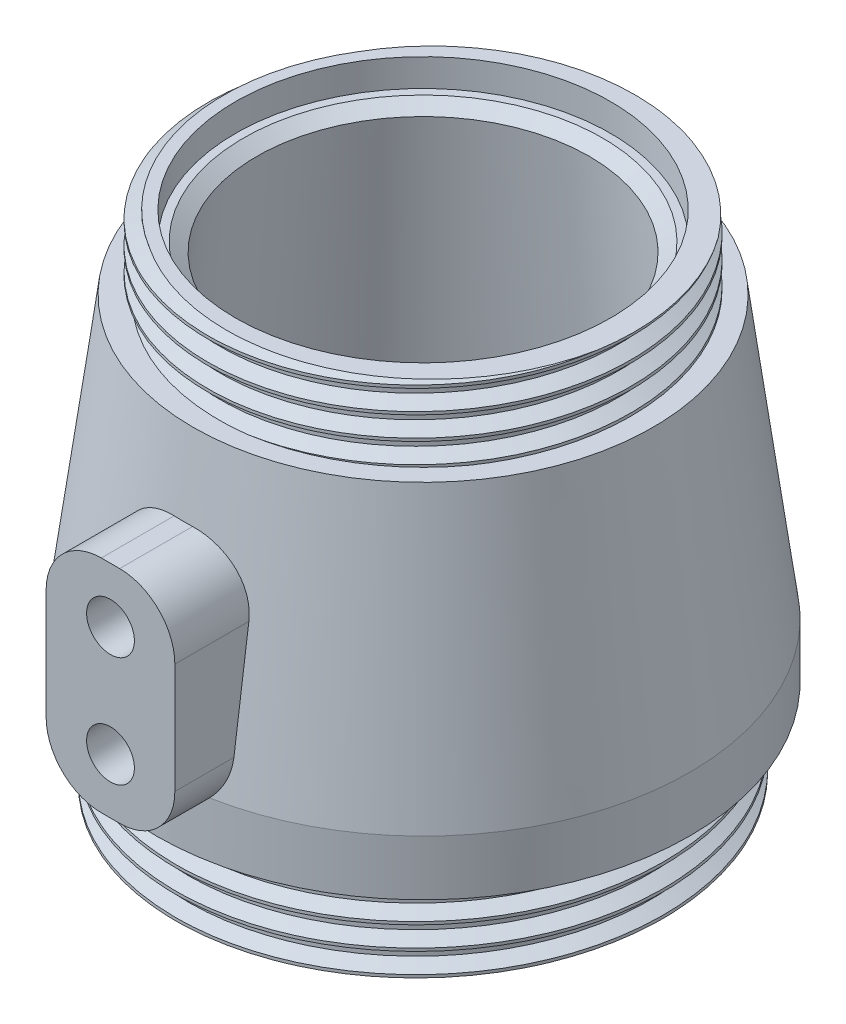
SolidWorks part; units mm, degrees
ref_plane "前视基准面" through (0, 0, 0) normal (0, 0, 1) x (1, 0, 0)
ref_plane "上视基准面" through (0, 0, 0) normal (0, 1, 0) x (1, 0, 0)
ref_plane "右视基准面" through (0, 0, 0) normal (1, 0, 0) x (0, 0, -1)
other "Configuration Table"
sketch "草图1" plane through (0, 0, 0) normal (0, 1, 0) x (1, 0, 0)
  circle A0 centre (0, 0) radius 13.25
  circle A1 centre (0, 0) radius 11
  dimension "D1" = 26.5
  dimension "D2" = 22
extrude "凸台-拉伸1" add sketch "草图1" along normal blind 25.75
sketch "草图2" plane through (0, 25.75, 0) normal (0, 1, 0) x (1, 0, 0)
  circle A0 centre (0, 0) radius 14.5
  circle A1 centre (0, 0) radius 13.25 construction
  circle A2 centre (0, 0) radius 13.25
  dimension "D1" = 29
extrude "凸台-拉伸2" add sketch "草图2" against normal offset from surface (20.75 mm away) 5 up to face at (0, 0, 13.25)
thread "螺纹线1" pitch 1.25 method cut trim with start face yes trim with end face yes profile "螺纹线轮廓1" start angle 0, offset 3, length 0, pitch 1.25, diameter 26.5
ref_plane "基准面1" through (13.25, -3, 0) normal (0, 0, 1) x (1, 0, 0)
sketch "螺纹线轮廓1" plane through (13.25, -3, 0) normal (0, 0, 1) x (1, 0, 0)
  line L0 (0, 0) -> (0, 1.25) construction
  line L11 (0, 0) -> (0, 1.0937)
  line L12 (0, 1.0937) -> (-0.6766, 0.7031)
  line L13 (-0.6766, 0.7031) -> (-0.6766, 0.3906)
  line L15 (-0.6766, 0.3906) -> (0, 0)
  line L17 (-0.6766, 0.5469) -> (0, 0.5469) construction
  point P2 (0, 0)
  dimension "Pitch" = 1.25
  dimension "Profile_Angle" = 60
  dimension "Profile_Land" = 0.3125
  dimension "Profile_Height" = 0.6766
sketch "草图5" plane through (0, 0, 0) normal (1, 0, 0) x (0, 0, -1)
  line L0 (9, 25.75) -> (11, 0)
  line L2 (11, 25.75) -> (-11, 25.75) construction
  line L3 (11, 0) -> (11, 25.75)
  line L4 (11, 25.75) -> (9, 25.75)
  line L6 (0, 0) -> (0, 25.75) construction
  dimension "D1" = 9
revolve "旋转1" add sketch "草图5" angle 360 about L6
chamfer "倒角1" distance 0.5 angle 60 1 edges at (0, 25.75, -9) first distance on face at (0, 0, -11)
sketch "草图6" plane through (0, 25.75, 0) normal (0, 1, 0) x (1, 0, 0)
  circle A0 centre (0, 0) radius 10.2
  circle A1 centre (0, 0) radius 11.5
  dimension "D1" = 20.4
  dimension "D2" = 23
extrude "凸台-拉伸3" add sketch "草图6" along normal blind 1.5
sketch "草图7" plane through (0, 25.75, 0) normal (0, 1, 0) x (1, 0, 0)
  circle A0 centre (0, 0) radius 11.5 construction
  circle A1 centre (0, 0) radius 14.5
  circle A2 centre (0, 0) radius 14.5
  circle A3 centre (0, 0) radius 11.5
  dimension "D1" = 0
extrude "切除-拉伸1" cut sketch "草图7" against normal offset from surface (2.5 mm away) 4 up to face at (0, 27.25, 11.5)
thread "螺纹线2" pitch 1.25 method cut trim with start face yes trim with end face yes profile "螺纹线轮廓2" start angle 0, offset 3, length 0, pitch 1.25, diameter 23
ref_plane "基准面2" through (-11.5, 30.25, 0) normal (0, 0, 1) x (-1, 0, 0)
sketch "螺纹线轮廓2" plane through (-11.5, 30.25, 0) normal (0, 0, 1) x (-1, 0, 0)
  line L0 (0, 0) -> (0, 1.25) construction
  line L11 (0, 0) -> (0, 1.0937)
  line L12 (0, 1.0937) -> (-0.6766, 0.7031)
  line L13 (-0.6766, 0.7031) -> (-0.6766, 0.3906)
  line L15 (-0.6766, 0.3906) -> (0, 0)
  line L17 (-0.6766, 0.5469) -> (0, 0.5469) construction
  point P2 (0, 0)
  dimension "Pitch" = 1.25
  dimension "Profile_Angle" = 60
  dimension "Profile_Land" = 0.3125
  dimension "Profile_Height" = 0.6766
sketch "草图11" plane through (0, 0, 0) normal (1, 0, 0) x (0, 0, -1)
  line L1 (14.5, 23.25) -> (-14.5, 23.25) construction
  line L2 (-12.5, 23.25) -> (-14.5, 23.25)
  line L3 (-14.5, 23.25) -> (-14.5, 8)
  line L4 (0, 0) -> (0, 23.25) construction
  line L5 (-12.5, 23.25) -> (-14.5, 8)
  line L6 (-14.5, 5) -> (14.5, 5) construction
  dimension "D1" = 12.5
  dimension "D2" = 3
revolve "切除-旋转1" cut sketch "草图11" angle 360 about L4
ref_plane "基准面3" through (0, 0, 17) normal (0, 0, 1) x (1, 0, 0)
sketch "草图12" plane through (0, 0, 17) normal (0, 0, 1) x (1, 0, 0)
  line L0 (0, 13.1) -> (0, 0) construction
  line L1 (-3.5, 19.1) -> (3.5, 19.1)
  line L2 (-3.5, 19.1) -> (-3.5, 7.1)
  line L3 (-3.5, 7.1) -> (3.5, 7.1)
  line L4 (3.5, 19.1) -> (3.5, 7.1)
  line L5 (-3.5, 19.1) -> (3.5, 7.1) construction
  line L6 (-3.5, 7.1) -> (3.5, 19.1) construction
  point P4 (0, 13.1)
  dimension "D1" = 7
  dimension "D2" = 13.1
  dimension "D3" = 12
extrude "凸台-拉伸4" add sketch "草图12" against normal up to next
sketch "草图13" plane through (0, 0, 17) normal (0, 0, 1) x (1, 0, 0)
  line L0 (0, 19.1) -> (0, 7.1) construction
  line L1 (3.5, 19.1) -> (-3.5, 19.1) construction
  line L2 (-3.5, 7.1) -> (3.5, 7.1) construction
  line L3 (0, 13.1) -> (3.5, 13.1) construction
  line L4 (3.5, 7.1) -> (3.5, 19.1) construction
  circle A0 centre (0, 16.1) radius 1.3
  circle A1 centre (0, 10.1) radius 1.3
  dimension "D1" = 2.6
  dimension "D2" = 6
extrude "切除-拉伸2" cut sketch "草图13" against normal blind 5
fillet "圆角1" radius 3 4 edges at (3.5, 7.1, 15.5356) (-3.5, 7.1, 15.5356) (-3.5, 19.1, 14.783) (3.5, 19.1, 14.783)
